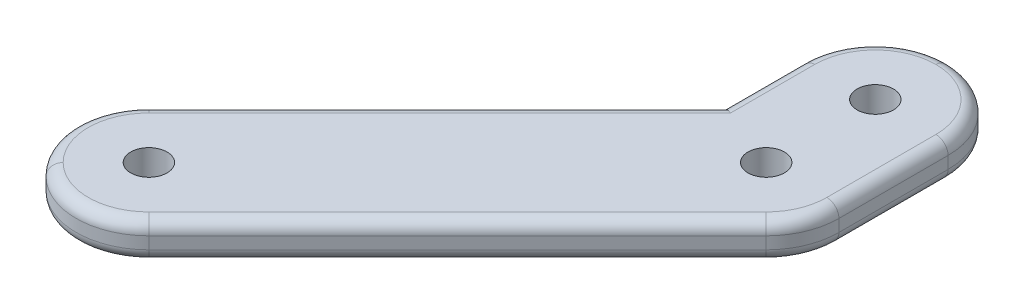
SolidWorks part; units mm, degrees
material "6061 Alloy"
ref_plane "Front Plane" through (0, 0, 0) normal (0, 0, 1) x (1, 0, 0)
ref_plane "Top Plane" through (0, 0, 0) normal (0, 1, 0) x (1, 0, 0)
ref_plane "Right Plane" through (0, 0, 0) normal (1, 0, 0) x (0, 0, -1)
sketch "Sketch1" plane through (0, 0, 0) normal (0, 1, 0) x (1, 0, 0)
  line L0 (0, 31.2053) -> (0, -31.2053) construction
  line L1 (-12.7, -31.2053) -> (12.7, -31.2053) construction
  line L2 (-12.7, -31.2053) -> (-12.7, 31.2053) construction
  line L3 (-12.7, 31.2053) -> (12.7, 31.2053)
  line L4 (12.7, -31.2053) -> (12.7, 31.2053) construction
  line L5 (-12.7, -31.2053) -> (12.7, 31.2053) construction
  line L6 (-12.7, 31.2053) -> (12.7, -31.2053) construction
  line L7 (-12.7, 4.7158) -> (-71.842, -54.4263)
  line L8 (-71.842, -54.4263) -> (-53.8815, -72.3868)
  line L9 (-53.8815, -72.3868) -> (-12.7, -31.2053)
  line L10 (-62.8618, -63.4065) -> (0, -0.5447)
  line L11 (-12.7, -31.2053) -> (8.9803, -9.525)
  line L12 (12.7, -0.5447) -> (12.7, 31.2053)
  line L13 (-12.7, 4.7158) -> (-12.7, 31.2053)
  circle A1 centre (0, -0.5447) radius 3.175
  circle A2 centre (0, 18.5053) radius 3.175
  circle A4 centre (0, -0.5447) radius 12.7
  circle A5 centre (-53.8815, -54.4263) radius 3.175
  point P0 (0, 0)
  dimension "D3" = 6.35
  dimension "D1" = 25.4
  dimension "D8" = 12.7
  dimension "D6" = 76.2
  dimension "D2" = 25.4
  dimension "D4" = 19.05
  dimension "D5" = 135
  dimension "D7" = 12.7
extrude "Boss-Extrude1" add sketch "Sketch1" along normal blind 6.35 contours A5 L10 A4 L12 L3 L13 L7 L8 A2 | A4 A1 | A5 L10 L8 L9 L11 A4 region at (-25.7104, 0, 13.0159) region at (11.4014, 0, 5.2674) region at (-29.983, 0, 39.7959)
fillet "Fillet2" radius 12.7 4 edges at (12.7, 3.175, -31.2053) (-12.7, 3.175, -31.2053) (-71.842, 3.175, 54.4263) (-53.8815, 3.175, 72.3868)
fillet "Fillet3" radius 2.1167 18 edges at (-12.7, 0, -11.6105) (-8.9803, 0, -27.4855) (8.9803, 0, -27.4855) (12.7, 0, -8.9803) (11.7333, 0, 5.4048) (-17.9605, 0, 36.4658) (-53.8815, 0, 67.1263) (-66.5815, 0, 54.4263) (-12.7, 6.35, -11.6105) (-8.9803, 6.35, -27.4855) (8.9803, 6.35, -27.4855) (12.7, 6.35, -8.9803) (11.7333, 6.35, 5.4048) (-17.9605, 6.35, 36.4658) (-53.8815, 6.35, 67.1263) (-66.5815, 6.35, 54.4263) (-37.7809, 0, 20.3651) (-37.7809, 6.35, 20.3651)
